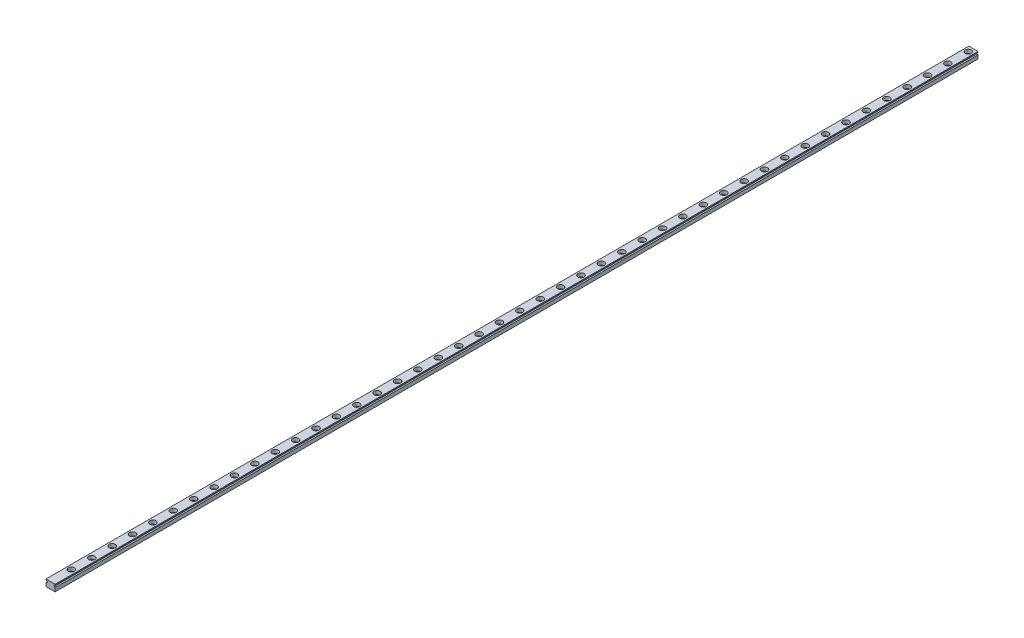
SolidWorks part; units mm, degrees
ref_plane "Front Plane" through (0, 0, 0) normal (0, 0, 1) x (1, 0, 0)
ref_plane "Top Plane" through (0, 0, 0) normal (0, 1, 0) x (1, 0, 0)
ref_plane "Right Plane" through (0, 0, 0) normal (1, 0, 0) x (0, 0, -1)
sketch "Sketch1" plane through (0, 0, 0) normal (0, 0, 1) x (1, 0, 0)
  line L0 (0, 0) -> (0, 5.7299) construction
  line L1 (-4.5, -3.25) -> (4.5, -3.25)
  line L2 (-4.5, -3.25) -> (-4.5, 0.25)
  line L3 (-4.5, 3.25) -> (4.5, 3.25)
  line L4 (4.5, -3.25) -> (4.5, 0.25)
  line L5 (-4.5, -3.25) -> (4.5, 3.25) construction
  line L6 (-4.5, 3.25) -> (4.5, -3.25) construction
  line L7 (-4.5, 2.25) -> (-4.5, 3.25)
  line L8 (-3.564, 0.898) -> (-3.2351, 0.898)
  line L9 (3.564, 0.898) -> (3.2351, 0.898)
  line L10 (-3.564, 1.602) -> (-3.2351, 1.602)
  line L11 (-3.2351, 0.898) -> (-3.2351, 1.602)
  line L12 (3.2351, 0.898) -> (3.2351, 1.602)
  line L13 (3.564, 1.602) -> (3.2351, 1.602)
  line L14 (4.5, 2.25) -> (4.5, 3.25)
  arc A0 (-3.564, 1.602) -> (-4.5, 2.25) centre (-4.5, 1.25) ccw
  arc A1 (-4.5, 0.25) -> (-3.564, 0.898) centre (-4.5, 1.25) ccw
  arc A2 (4.5, 0.25) -> (3.564, 0.898) centre (4.5, 1.25) cw
  arc A3 (3.564, 1.602) -> (4.5, 2.25) centre (4.5, 1.25) cw
  point P0 (0, 0)
  dimension "D3" = 1
  dimension "D1" = 9
  dimension "D2" = 6.5
  dimension "D4" = 2
extrude "Extrude1" add sketch "Sketch1" along normal blind 905.4
sketch "Sketch2" plane through (0, 3.25, 0) normal (0, 1, 0) x (1, 0, 0)
  line L0 (4.5, 0) -> (-4.5, 0) construction
  circle A0 centre (0, -5) radius 1.75
  circle A1 centre (0, -5) radius 3
  dimension "D1" = 3.5
  dimension "D2" = 6
  dimension "D3" = 5
extrude "Extrude2" cut sketch "Sketch2" against normal blind 3.5 contours A1
extrude "Extrude3" cut sketch "Sketch" against normal through all contours A0
sketch "Sketch" plane through (0, 3.25, 0) normal (0, 1, 0) x (1, 0, 0) same geometry as "Sketch2"
pattern_linear "LPattern1" count 45 spacing 20 along (0, 0, 1) of "Extrude2", "Extrude3"
